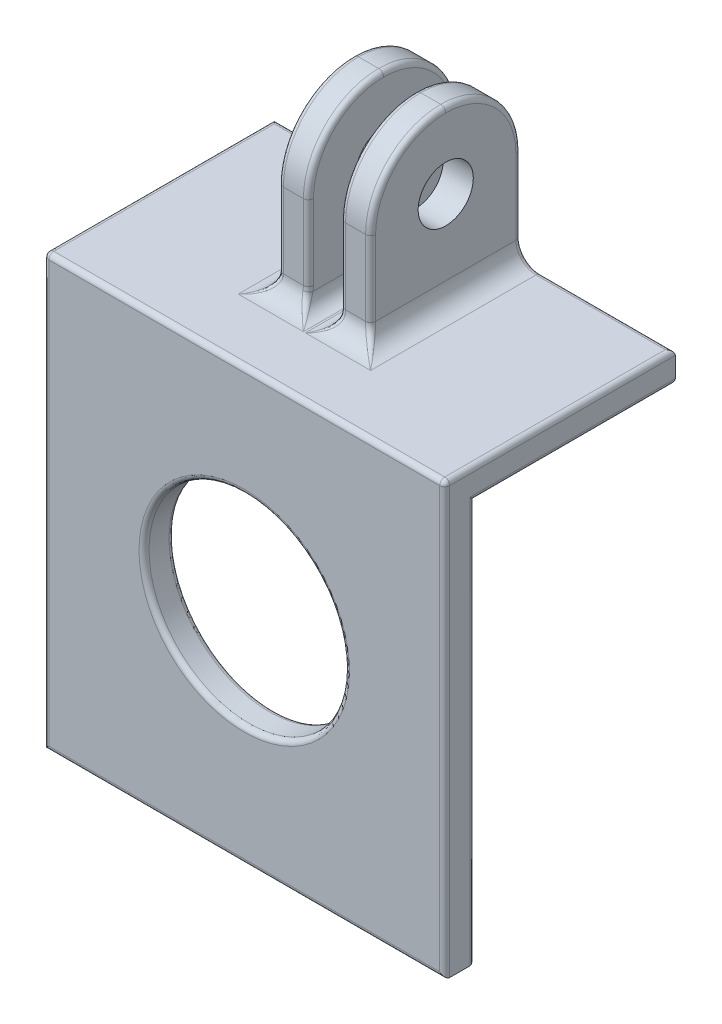
SolidWorks part; units mm, degrees
ref_plane "Ebene vorne" through (0, 0, 0) normal (0, 0, 1) x (1, 0, 0)
ref_plane "Ebene oben" through (0, 0, 0) normal (0, 1, 0) x (1, 0, 0)
ref_plane "Ebene rechts" through (0, 0, 0) normal (1, 0, 0) x (0, 0, -1)
sketch "Skizze1" plane through (0, 0, 0) normal (1, 0, 0) x (0, 0, -1)
  line L0 (0, 5.45) -> (0, 25326.7564) construction
  line L2 (0, 0) -> (25321.3064, 0) construction
  line L4 (7.1, 21.05) -> (-15.9, 21.05)
  line L5 (-15.9, 21.05) -> (-15.9, -21.95)
  line L6 (-15.9, -21.95) -> (-12.9, -21.95)
  line L7 (-12.9, -21.95) -> (-12.9, 18.05)
  line L8 (-12.9, 18.05) -> (7.1, 18.05)
  line L9 (7.1, 18.05) -> (7.1, 21.05)
  dimension "D1" = 3
  dimension "D2" = 3
  dimension "D3" = 40
  dimension "D4" = 20
extrude "Aufsatz-Linear austragen1" add sketch "Skizze1" along normal mid plane 40
sketch "Skizze2" plane through (0, 21.05, 0) normal (0, 1, 0) x (1, 0, 0)
  line L0 (-4.6, 7.1) -> (-1.6, 7.1)
  line L1 (-4.6, 7.1) -> (-4.6, -7.9)
  line L2 (-4.6, -7.9) -> (-1.6, -7.9)
  line L3 (4.6, 7.1) -> (4.6, -7.9)
  line L4 (-1.6, 7.1) -> (-1.6, -7.9)
  line L5 (1.6, 7.1) -> (1.6, -7.9)
  line L6 (1.6, 7.1) -> (4.6, 7.1)
  line L7 (1.6, -7.9) -> (4.6, -7.9)
  line L8 (20, 7.1) -> (-20, 7.1) construction
  line L9 (0, -12.65) -> (0, 12.65) construction
  point P8 (-3.1, 7.1)
  dimension "D1" = 15
  dimension "D2" = 3.2
  dimension "D3" = 0
  dimension "D4" = 1.6
  dimension "D5" = 3
  dimension "D6" = 3
extrude "Aufsatz-Linear austragen2" add sketch "Skizze2" along normal blind 17
fillet "Verrundung1" radius 7.5 4 edges at (3.1, 38.05, -7.1) (-3.1, 38.05, -7.1) (3.1, 38.05, 7.9) (-3.1, 38.05, 7.9)
sketch "Skizze3" plane through (4.6, 0, 0) normal (1, 0, 0) x (0, 0, -1)
  circle A0 centre (-0.4, 30.55) radius 2.75
  dimension "D1" = 5.5
extrude "Schnitt-Linear austragen1" cut sketch "Skizze3" against normal through all
fillet "Verrundung2" radius 2 4 edges at (-4.6, 21.05, 0.4) (-3.1, 21.05, 7.9) (3.1, 21.05, 7.9) (4.6, 21.05, 0.4)
fillet "Verrundung3" radius 1.5 2 edges at (1.6, 21.05, 1.4) (-1.6, 21.05, 1.4)
fillet "Verrundung4" radius 0.5 41 edges at (-5.1858, 21.6358, 8.4858) (-4.6, 26.8, 7.9) (-13.3, 21.05, -7.1) (-5.1858, 21.6358, -7.1) (-4.6, 26.8, -7.1) (-4.6, 35.8533, -4.9033) (1.3553, 21.7288, 8.3985) (1.6, 22.798, 7.9159) (1.6, 26.8, 7.9) (1.6, 35.8533, 5.7033) (1.6, 35.8533, -4.9033) (1.6, 26.55, -7.1) (1.1607, 21.4893, -7.1) (0, 21.05, -7.1) (-1.1607, 21.4893, -7.1) (-1.6, 26.55, -7.1) (-1.6, 35.8533, -4.9033) (-1.6, 35.8533, 5.7033) (-1.3553, 21.7288, 8.3985) (-1.6, 22.798, 7.9159) (13.3, 21.05, -7.1) (5.1858, 21.6358, -7.1) (4.6, 26.8, -7.1) (4.6, 35.8533, -4.9033) (4.6, 35.8533, 5.7033) (5.1858, 21.6358, 8.4858) (-20, 18.05, 2.9) (0, 18.05, -7.1) (20, 18.05, 2.9) (20, -1.95, 12.9) (0, -21.95, 12.9) (-20, -1.95, 12.9) (0, -21.95, 15.9) (20, -0.45, 15.9) (-20, -0.45, 15.9) (20, 21.05, 4.4) (0, 21.05, 15.9) (-20, 21.05, 4.4) (-4.6, 35.8533, 5.7033) (-1.6, 26.8, 7.9) (4.6, 26.8, 7.9)
sketch "Skizze4" plane through (0, 0, 15.9) normal (0, 0, 1) x (1, 0, 0)
  circle A0 centre (0, 0) radius 10
  dimension "D1" = 20
extrude "Schnitt-Linear austragen2" cut sketch "Skizze4" against normal through all
fillet "Verrundung5" radius 0.5 2 edges at (10, 0, 12.9) (10, 0, 15.9)
